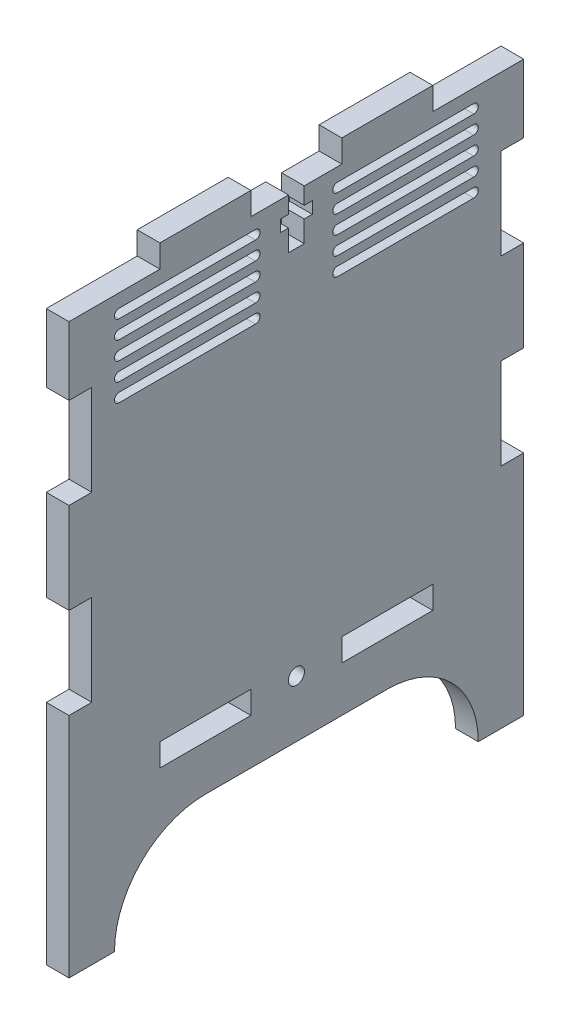
SolidWorks part; units mm, degrees
ref_plane "Front Plane" through (0, 0, 0) normal (0, 0, 1) x (1, 0, 0)
ref_plane "Top Plane" through (0, 0, 0) normal (0, 1, 0) x (1, 0, 0)
ref_plane "Right Plane" through (0, 0, 0) normal (1, 0, 0) x (0, 0, -1)
sketch "Sketch1" plane through (0, 0, 0) normal (1, 0, 0) x (0, 0, -1)
  line L1 (-63.5, 82.55) -> (63.5, 82.55)
  line L2 (-63.5, 82.55) -> (-63.5, -82.55)
  line L3 (-63.5, -82.55) -> (63.5, -82.55)
  line L4 (63.5, 82.55) -> (63.5, -82.55)
  line L5 (-63.5, 82.55) -> (63.5, -82.55) construction
  line L6 (-63.5, -82.55) -> (63.5, 82.55) construction
  point P0 (0, 0)
  dimension "D1" = 127
  dimension "D2" = 165.1
extrude "Boss-Extrude1" add sketch "Sketch1" along normal blind 6.35
sketch "Sketch2" plane through (6.35, 0, 0) normal (1, 0, 0) x (0, 0, -1)
  line L1 (-63.5, 82.55) -> (-38.1, 82.55)
  line L2 (-63.5, 82.55) -> (-63.5, 76.2)
  line L3 (-63.5, 76.2) -> (-38.1, 76.2)
  line L4 (-38.1, 82.55) -> (-38.1, 76.2)
  dimension "D1" = 25.4
  dimension "D2" = 6.35
extrude "Cut-Extrude1" cut sketch "Sketch2" against normal blind 6.35
pattern_linear "LPattern1" count 3 spacing 50.8 along (0, 0, -1) of "Cut-Extrude1"
sketch "Sketch5" plane through (6.35, 0, 0) normal (1, 0, 0) x (0, 0, -1)
  line L0 (-25.4, -82.55) -> (25.4, -82.55) construction
  line L1 (-63.5, -82.55) -> (63.5, -82.55) construction
  line L2 (-25.4, -57.15) -> (25.4, -57.15)
  line L3 (-25.4, -107.95) -> (25.4, -107.95)
  arc A0 (-25.4, -57.15) -> (-25.4, -107.95) centre (-25.4, -82.55) ccw
  arc A1 (25.4, -107.95) -> (25.4, -57.15) centre (25.4, -82.55) ccw
  point P4 (0, -82.55)
  dimension "D2" = 25.4
  dimension "D1" = 50.8
extrude "Cut-Extrude4" cut sketch "Sketch5" against normal blind 6.35
sketch "Sketch8" plane through (6.35, 0, 0) normal (1, 0, 0) x (0, 0, -1)
  line L0 (63.5, -82.55) -> (63.5, 76.2) construction
  line L1 (63.5, 57.15) -> (57.15, 57.15)
  line L2 (63.5, 57.15) -> (63.5, 31.75)
  line L3 (63.5, 31.75) -> (57.15, 31.75)
  line L4 (57.15, 57.15) -> (57.15, 31.75)
  line L5 (38.1, 82.55) -> (12.7, 82.55) construction
  dimension "D1" = 25.4
  dimension "D2" = 25.4
  dimension "D3" = 6.35
extrude "Cut-Extrude6" cut sketch "Sketch8" against normal blind 6.35
pattern_linear "LPattern4" count 2 spacing 50.8 along (0, -1, 0) of "Cut-Extrude6"
ref_plane "Plane1" through (0, 0, 0) normal (0, 0, 1) x (1, 0, 0)
mirror "Mirror1" about plane through (0, 0, 0) normal (0, 0, 1) of "LPattern4"
sketch "Sketch9" plane through (0, 0, 0) normal (-1, 0, 0) x (0, 0, 1)
  line L0 (-63.5, -82.55) -> (-63.5, -19.05) construction
  line L1 (-38.1, -38.1) -> (-12.7, -38.1)
  line L2 (-38.1, -38.1) -> (-38.1, -44.45)
  line L3 (-38.1, -44.45) -> (-12.7, -44.45)
  line L4 (-12.7, -38.1) -> (-12.7, -44.45)
  line L5 (-38.1, 82.55) -> (-12.7, 82.55) construction
  point P6 (-25.4, 82.55)
  dimension "D1" = 25.4
  dimension "D2" = 6.35
  dimension "D3" = 25.4
  dimension "D4" = 120.65
extrude "Cut-Extrude7" cut sketch "Sketch9" against normal blind 6.35
pattern_linear "LPattern6" count 2 spacing 50.8 along (0, 0, 1) of "Cut-Extrude7"
sketch "Sketch16" plane through (0, 0, 0) normal (-1, 0, 0) x (0, 0, 1)
  line L0 (12.7, 76.2) -> (-12.7, 76.2) construction
  line L1 (-2.1971, 76.2) -> (2.1971, 76.2)
  line L2 (-2.1971, 76.2) -> (-2.1971, 62.23)
  line L3 (-2.1971, 62.23) -> (2.1971, 62.23)
  line L4 (2.1971, 76.2) -> (2.1971, 62.23)
  line L5 (-12.7, 76.2) -> (-12.7, 82.55) construction
  line L7 (-4.445, 71.501) -> (4.445, 71.501)
  line L8 (-4.445, 71.501) -> (-4.445, 68.199)
  line L9 (-4.445, 68.199) -> (4.445, 68.199)
  line L10 (4.445, 71.501) -> (4.445, 68.199)
  point P6 (0, 62.23)
  point P13 (0, 71.501)
  point P14 (4.445, 69.85)
  dimension "D1" = 4.3942
  dimension "D2" = 13.97
  dimension "D3" = 12.7
  dimension "D4" = 3.302
  dimension "D5" = 8.89
  dimension "D6" = 12.7
  dimension "D7" = 6.35
extrude "Cut-Extrude14" cut sketch "Sketch16" against normal blind 6.35 contours L7 L10 L9 L8 | L1 L4 L3 L2
hole_wizard "#8 Clearance Hole1" positions "Sketch18" profile "Sketch17" hole size "#8" standard "ANSI Inch"
sketch "Sketch18" plane through (0, 0, 0) normal (-1, 0, 0) x (0, 0, 1)
  line L3 (-12.7, -44.45) -> (-12.7, -38.1) construction
  line L4 (38.1, -38.1) -> (12.7, -38.1) construction
  point P0 (0, -41.275)
  point P16 (-12.7, -41.275)
  dimension "D1" = 12.7
  dimension "D2" = 3.175
sketch "Sketch17" plane through (0, -41.275, 0) normal (0, 1, 0) x (0, 0, 1)
  line L0 (0, 0) -> (0, 11.5107)
  line L1 (0, 11.5107) -> (2.2479, 10.16)
  line L2 (2.2479, 10.16) -> (2.2479, 0)
  line L5 (2.2479, 0) -> (0, 0)
  line L10 (0, 11.5107) -> (-2.2479, 10.16) construction
  line L11 (0, -6.35) -> (0, 107.95) construction
  dimension "Hole Dia." = 4.4958
  dimension "Hole Depth" = 10.16
  dimension "Drill Angle" = 118
sketch "Sketch19" plane through (0, 0, 0) normal (-1, 0, 0) x (0, 0, 1)
  line L0 (-49.53, 71.1789) -> (-11.43, 71.1789) construction
  line L1 (-49.53, 72.4489) -> (-11.43, 72.4489)
  line L2 (-49.53, 69.9089) -> (-11.43, 69.9089)
  line L3 (-38.1, 82.55) -> (-38.1, 76.2) construction
  arc A0 (-49.53, 72.4489) -> (-49.53, 69.9089) centre (-49.53, 71.1789) ccw
  arc A1 (-11.43, 69.9089) -> (-11.43, 72.4489) centre (-11.43, 71.1789) ccw
  point P2 (-30.48, 71.1789)
  point P7 (-30.48, 72.4489)
  dimension "D2" = 1.27
  dimension "D1" = 38.1
  dimension "D3" = 7.62
extrude "Cut-Extrude15" cut sketch "Sketch19" against normal blind 6.35
mirror "Mirror2" about plane through (0, 0, 0) normal (0, 0, 1) of "Cut-Extrude15"
pattern_linear "LPattern7" count 5 spacing 5.08 along (0, -1, 0) of "Mirror2"
